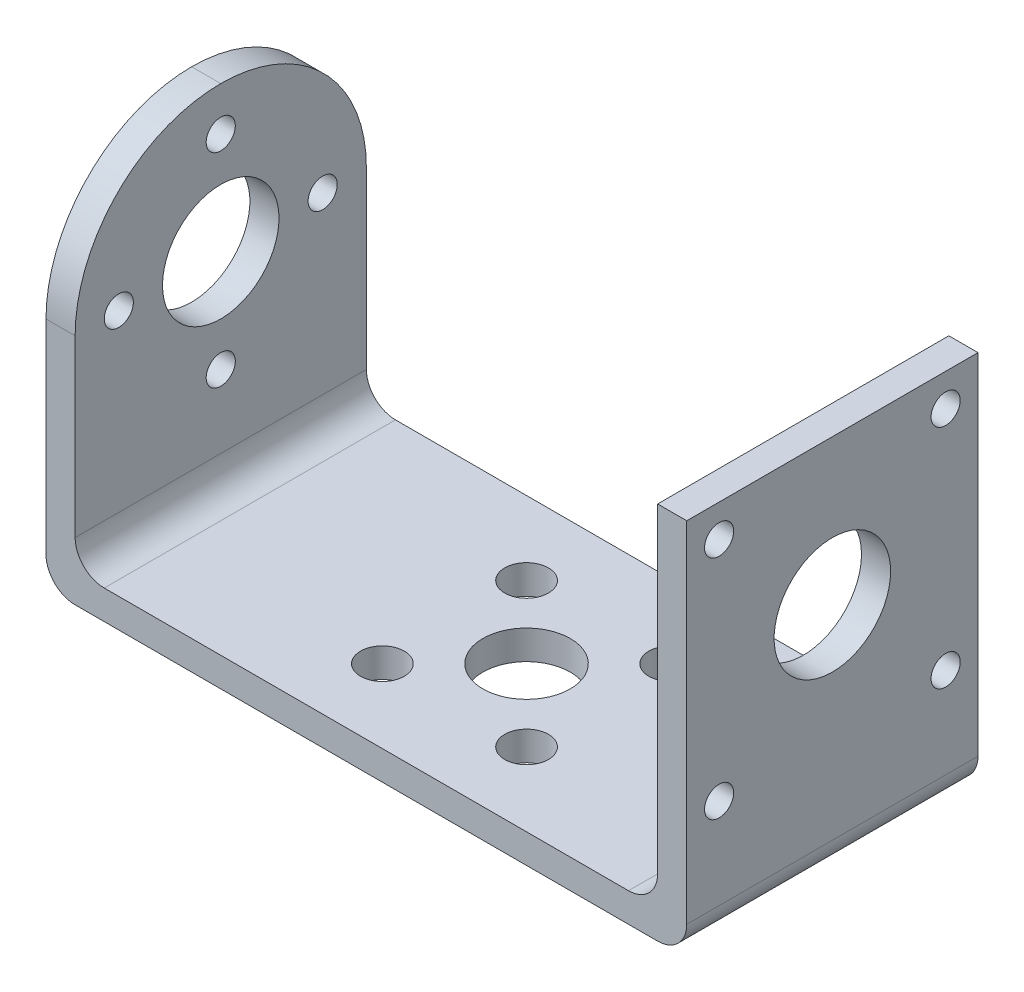
SolidWorks part; units mm, degrees
ref_plane "Спереди" through (0, 0, 0) normal (0, 0, 1) x (1, 0, 0)
ref_plane "Сверху" through (0, 0, 0) normal (0, 1, 0) x (1, 0, 0)
ref_plane "Справа" through (0, 0, 0) normal (1, 0, 0) x (0, 0, -1)
sketch "Sketch1" plane through (0, 0, 0) normal (0, 0, 1) x (1, 0, 0)
  line L0 (0, 0) -> (44, 0)
  line L1 (44, 0) -> (44, 26)
  line L2 (44, 26) -> (42, 26)
  line L3 (42, 26) -> (42, 2)
  line L4 (2, 2) -> (42, 2)
  line L5 (2, 2) -> (2, 26)
  line L6 (2, 26) -> (0, 26)
  line L7 (0, 26) -> (0, 0)
  dimension "D1" = 44
  dimension "D2" = 26
  dimension "D3" = 2
  dimension "D4" = 2
  dimension "D5" = 24
  dimension "D6" = 2
extrude "Основа" add sketch "Sketch1" along normal blind 20
sketch "Sketch2" plane through (0, 0, 0) normal (-1, 0, 0) x (0, 0, 1)
  line L0 (10, 16) -> (10, 23) construction
  line L1 (0, 0) -> (10, 0) construction
  line L2 (20, 0) -> (0, 0) construction
  line L5 (10, 0) -> (10, 16) construction
  line L6 (10, 16) -> (10, 9) construction
  circle A0 centre (10, 16) radius 4
  circle A1 centre (10, 23) radius 1
  circle A2 centre (17, 16) radius 1
  circle A3 centre (10, 9) radius 1
  circle A4 centre (3, 16) radius 1
  point P16 (10, 16)
  dimension "D1" = 8
  dimension "D4" = 2
  dimension "D2" = 7
  dimension "D5" = 16
  dimension "D6" = 7
  dimension "D3" = 4
extrude "Отверстия под ось и винты 1" cut sketch "Sketch2" against normal blind 2
sketch "Sketch3" plane through (44, 0, 0) normal (1, 0, 0) x (0, 0, -1)
  line L2 (0, 26) -> (0, 6)
  line L3 (0, 0) -> (0, 26) construction
  circle A0 centre (-10, 16) radius 4
  circle A1 centre (-2.2218, 23.7782) radius 1
  circle A2 centre (-2.2218, 8.2218) radius 1
  circle A3 centre (-17.7782, 8.2218) radius 1
  circle A4 centre (-17.7782, 23.7782) radius 1
  point P28 (-10, 16)
extrude "Отверстия под ось и винты 2" cut sketch "Sketch3" against normal blind 20 contours A4 | A0 | A1 | A2 | A3 region at (44, 16, 10) region at (44, 23.7782, 2.2218) region at (44, 8.2218, 2.2218) region at (44, 8.2218, 17.7782) region at (44, 23.7782, 17.7782)
sketch "Sketch4" plane through (0, 0, 0) normal (0, -1, 0) x (1, 0, 0)
  line L0 (0, 0) -> (46, 0) construction
  line L1 (23, 10) -> (23, 0)
  line L2 (23, 10) -> (27.9497, 5.0503) construction
  circle A0 centre (23, 10) radius 3
  circle A1 centre (18.0503, 5.0503) radius 1.5
  circle A2 centre (27.9497, 5.0503) radius 1.5
  circle A3 centre (18.0503, 14.9497) radius 1.5
  circle A4 centre (27.9497, 14.9497) radius 1.5
  circle A5 centre (23, 10) radius 7 construction
  point P11 (23, 10)
  point P17 (23, 10)
  dimension "D1" = 6
  dimension "D4" = 45
  dimension "D6" = 4
  dimension "D5" = 3
  dimension "D7" = 14
  dimension "D2" = 10
  dimension "D3" = 23
extrude "Отверстия под крепёж" cut sketch "Sketch4" against normal blind 2 contours A0 | A4 | A3 | A1 | A2 region at (25.0613, 0, 7.9387) region at (18.0503, 0, 5.0503) region at (27.9497, 0, 5.0503) region at (18.0503, 0, 14.9497) region at (27.9497, 0, 14.9497)
fillet "Fillet1" radius 10 2 edges at (1, 26, 0) (1, 26, 20)
fillet "Fillet2" radius 2 4 edges at (0, 0, 10) (42, 2, 10) (2, 2, 10) (44, 0, 10)
